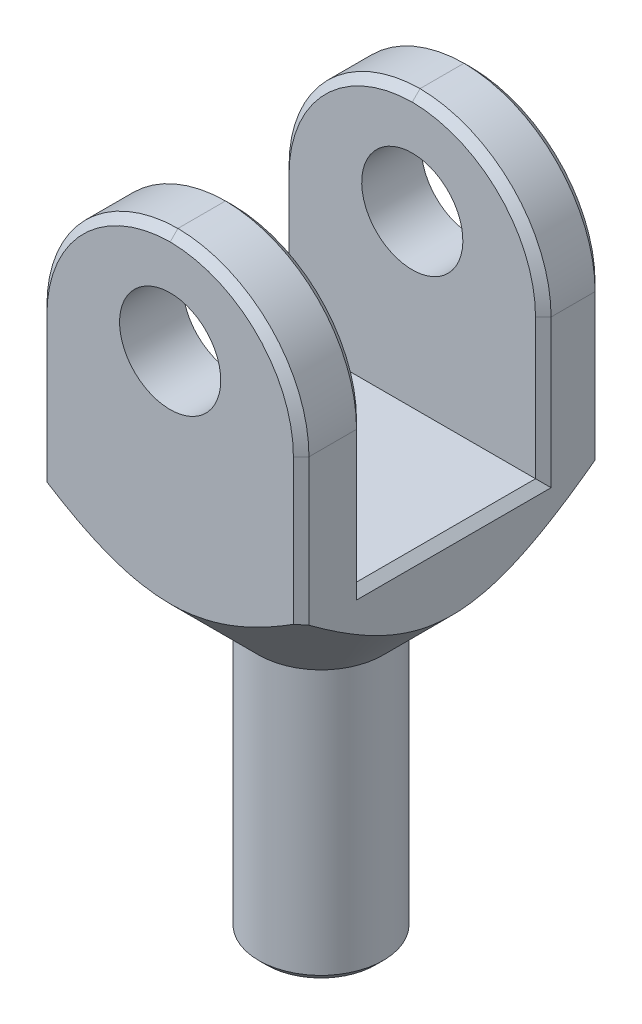
SolidWorks part; units mm, degrees
ref_plane "Front Plane" through (0, 0, 0) normal (0, 0, 1) x (1, 0, 0)
ref_plane "Top Plane" through (0, 0, 0) normal (0, 1, 0) x (1, 0, 0)
ref_plane "Right Plane" through (0, 0, 0) normal (1, 0, 0) x (0, 0, -1)
sketch "Sketch1" plane through (0, 0, 0) normal (0, 1, 0) x (1, 0, 0)
  circle A0 centre (0, 0) radius 80
  dimension "D1" = 160
extrude "Boss-Extrude1" add sketch "Sketch1" along normal blind 350
sketch "Sketch2" plane through (0, 0, 0) normal (0, 0, 1) x (1, 0, 0)
  line L0 (-80, 350) -> (-256.7767, 526.7767)
  line L1 (-256.7767, 526.7767) -> (-256.7767, 876.7767)
  line L2 (-256.7767, 876.7767) -> (0, 876.7767)
  line L3 (0, 876.7767) -> (0, 350)
  line L4 (80, 350) -> (-80, 350) construction
  line L5 (-80, 350) -> (0, 350)
  dimension "D1" = 45
  dimension "D2" = 350
revolve "Revolve1" add sketch "Sketch2" angle 360 about L3
sketch "Sketch3" plane through (0, 0, 0) normal (0, 0, 1) x (1, 0, 0)
  line L0 (-80, 350) -> (-256.7767, 526.7767) construction
  line L1 (-256.7767, 526.7767) -> (-256.7767, 350) construction
  line L2 (-256.7767, 350) -> (-80, 350) construction
  line L3 (-168.3883, 350) -> (-168.3883, 897.1199) construction
  line L4 (-168.3883, 897.1199) -> (-256.7767, 897.1199) construction
  line L5 (-256.7767, 897.1199) -> (-256.7767, 526.7767) construction
  line L6 (-256.7767, 350) -> (-256.7767, 897.1199)
  line L8 (-256.7767, 897.1199) -> (-168.3883, 897.1199)
  line L9 (168.3883, 897.1199) -> (256.7767, 897.1199) construction
  line L10 (256.7767, 897.1199) -> (256.7767, 526.7767) construction
  line L11 (168.3883, 350) -> (168.3883, 897.1199) construction
  line L12 (256.7767, 350) -> (80, 350) construction
  line L13 (256.7767, 526.7767) -> (256.7767, 350) construction
  line L14 (-168.3883, 897.1199) -> (-168.3883, 350)
  line L15 (-168.3883, 350) -> (-256.7767, 350)
  line L16 (168.3883, 350) -> (256.7767, 350)
  line L17 (256.7767, 350) -> (256.7767, 897.1199)
  line L18 (256.7767, 897.1199) -> (168.3883, 897.1199)
  line L19 (168.3883, 897.1199) -> (168.3883, 350)
extrude "Cut-Extrude1" cut sketch "Sketch3" against normal blind 280 and the other way blind 280
sketch "Sketch4" plane through (0, 0, 0) normal (1, 0, 0) x (0, 0, -1)
  line L0 (-193.8547, 876.7767) -> (-193.8547, 347.0512)
  line L1 (-193.8547, 347.0512) -> (-272.7515, 347.0512)
  line L2 (-272.7515, 347.0512) -> (-272.7515, 876.7767)
  line L3 (-272.7515, 876.7767) -> (-193.8547, 876.7767)
  line L4 (0, 350) -> (0, 876.7767) construction
  line L5 (-80, 350) -> (80, 350) construction
  line L6 (-193.8547, 876.7767) -> (193.8547, 876.7767) construction
  line L7 (272.7515, 876.7767) -> (193.8547, 876.7767)
  line L8 (193.8547, 347.0512) -> (272.7515, 347.0512)
  line L9 (272.7515, 347.0512) -> (272.7515, 876.7767)
  line L10 (193.8547, 876.7767) -> (193.8547, 347.0512)
extrude "Cut-Extrude2" cut sketch "Sketch4" against normal blind 280 and the other way blind 280
sketch "Sketch7" plane through (168.3883, 0, 0) normal (1, 0, 0) x (0, 0, -1)
  line L0 (0, 350) -> (0, 876.7767) construction
  line L1 (-80, 350) -> (80, 350) construction
  line L2 (-193.8547, 876.7767) -> (193.8547, 876.7767) construction
  line L3 (0, 350) -> (-80, 350) construction
  line L4 (-80, 350) -> (-80, 876.7767) construction
  line L5 (-193.8547, 526.7767) -> (0, 526.7767) construction
  line L6 (0, 526.7767) -> (193.8547, 526.7767) construction
  line L7 (0, 350) -> (80, 350) construction
  line L8 (80, 350) -> (80, 876.7767) construction
  line L9 (80, 876.7767) -> (-80, 876.7767) construction
  line L10 (-193.8547, 526.7767) -> (-80, 526.7767) construction
  line L11 (-80, 526.7767) -> (-136.9273, 526.7767) construction
  line L12 (-136.9273, 526.7767) -> (-136.9273, 876.7767) construction
  line L13 (193.8547, 526.7767) -> (80, 526.7767) construction
  line L14 (80, 526.7767) -> (136.9273, 526.7767) construction
  line L15 (136.9273, 526.7767) -> (136.9273, 876.7767) construction
  line L21 (-112.6913, 526.7767) -> (117.3087, 526.7767)
  line L23 (-112.6913, 526.7767) -> (-112.6913, 876.7767)
  line L24 (-112.6913, 876.7767) -> (117.3087, 876.7767)
  line L25 (117.3087, 876.7767) -> (117.3087, 526.7767)
  dimension "D1" = 273.8547
extrude "Cut-Extrude5" cut sketch "Sketch7" against normal blind 400
fillet "Fillet1" radius 170 4 edges at (-168.3883, 876.7767, 153.273) (-168.3883, 876.7767, -155.5817) (168.3883, 876.7767, -155.5817) (168.3883, 876.7767, 153.273)
sketch "Sketch8" plane through (0, 0, 193.8547) normal (0, 0, 1) x (1, 0, 0)
  line L0 (0, 350) -> (0, 876.7691) construction
  line L1 (80, 350) -> (-80, 350) construction
  line L2 (0, 876.7691) -> (0, 613.3845) construction
  circle A0 centre (0, 745.0768) radius 65
extrude "Cut-Extrude6" cut sketch "Sketch8" against normal blind 512
chamfer "Chamfer1" distance 10 angle 45 18 edges at (-168.3883, 616.7767, 193.8547) (-119.165, 826.4137, 193.8547) (119.165, 826.4137, 193.8547) (168.3883, 616.7767, 193.8547) (-168.3883, 616.7767, 112.6913) (-168.3883, 616.7767, -117.3087) (-119.165, 826.4137, 112.6913) (119.165, 826.4137, 112.6913) (-119.165, 826.4137, -117.3087) (119.165, 826.4137, -117.3087) (168.3883, 616.7767, 112.6913) (168.3883, 526.7767, -2.3087) (168.3883, 616.7767, -117.3087) (0, 0, 80) (168.3883, 616.7767, -193.8547) (119.165, 826.4137, -193.8547) (-168.3883, 616.7767, -193.8547) (-119.165, 826.4137, -193.8547)
ref_axis "Axis2" through (0, 745.0768, 112.6913) along (0, 0, 1)
ref_point "Point2"
